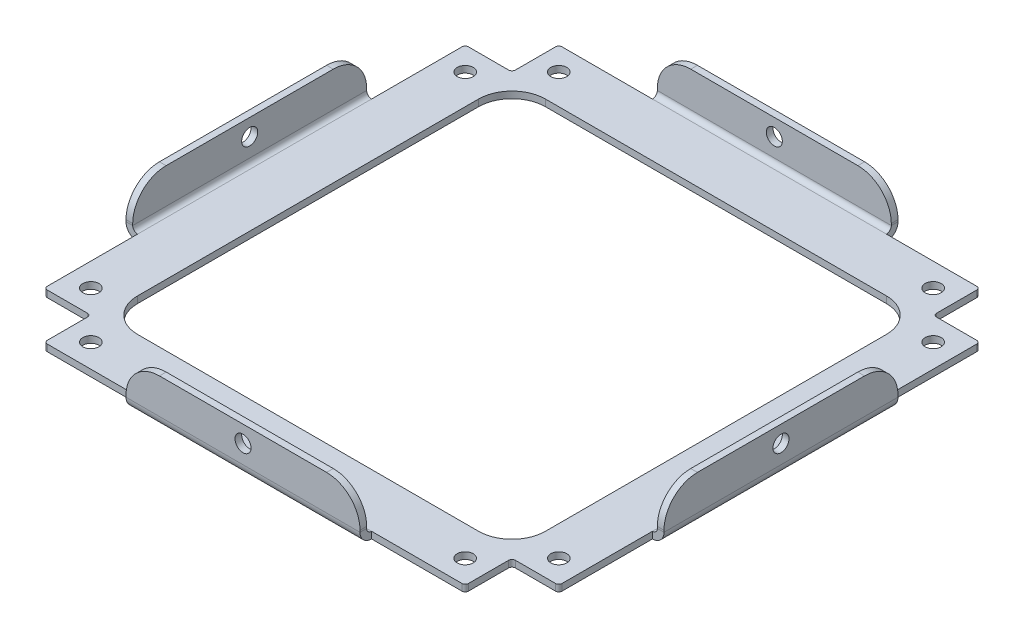
SolidWorks part; units mm, degrees
note: The reader was unsure of these and kept them because the rebuilt part matched: flange length of "Edge-Flange1", "Edge-Flange2", "Edge-Flange3", "Edge-Flange4".
material "6061 Alloy"
ref_plane "Frontal" through (0, 0, 0) normal (0, 0, 1) x (1, 0, 0)
ref_plane "Superior" through (0, 0, 0) normal (0, 1, 0) x (1, 0, 0)
ref_plane "Direito" through (0, 0, 0) normal (1, 0, 0) x (0, 0, -1)
sketch "Sketch1" plane through (0, 0, 0) normal (0, 1, 0) x (1, 0, 0)
  line L1 (-38.5, -38.5) -> (38.5, -38.5)
  line L2 (-38.5, -38.5) -> (-38.5, 38.5)
  line L3 (-38.5, 38.5) -> (38.5, 38.5)
  line L4 (38.5, -38.5) -> (38.5, 38.5)
  line L5 (-38.5, -38.5) -> (38.5, 38.5) construction
  line L6 (-38.5, 38.5) -> (38.5, -38.5) construction
  point P0 (0, 0)
  dimension "D1" = 77
  dimension "D2" = 77
base flange "Base-Flange1" sketch "Sketch1" thickness 1 reverse thickness direction no parameters "D1"=0.7366
edge flange "Edge-Flange1" sketch "Sketch8" flange angle 90 flange length 6 flange position bend outside bend radius 0.7366 thickness 1 relief rectangular parameters "D6"=10
sketch "Sketch8" plane through (0, 0, 38.5) normal (0, 0, 1) x (1, 0, 0)
  line L0 (-38.5, 0) -> (38.5, 0) construction
  line L1 (-17.5, 0) -> (17.5, 0)
  line L2 (-17.5, 0) -> (-17.5, 6)
  line L3 (-17.5, 6) -> (17.5, 6)
  line L4 (17.5, 6) -> (17.5, 0)
  point P6 (0, 0)
  dimension "D1" = 6
  dimension "D2" = 35
bend "EdgeBend1" bend radius 0.7366 bend angle 90 parameters "D5"=1
edge flange "Edge-Flange2" sketch "Sketch11" flange angle 90 flange length 6 flange position bend outside bend radius 0.7366 thickness 1 relief rectangular parameters "D6"=10
sketch "Sketch11" plane through (0, 0, -38.5) normal (0, 0, -1) x (-1, 0, 0)
  line L0 (-38.5, 0) -> (38.5, 0) construction
  line L1 (-17.5, 0) -> (17.5, 0)
  line L2 (-17.5, 0) -> (-17.5, 6)
  line L3 (-17.5, 6) -> (17.5, 6)
  line L4 (17.5, 6) -> (17.5, 0)
  point P6 (0, 0)
  dimension "D1" = 6
  dimension "D2" = 35
bend "EdgeBend2" bend radius 0.7366 bend angle 90 parameters "D5"=2
edge flange "Edge-Flange3" sketch "Sketch14" flange angle 90 flange length 6 flange position bend outside bend radius 0.7366 thickness 1 relief rectangular parameters "D6"=10
sketch "Sketch14" plane through (-38.5, 0, 0) normal (-1, 0, 0) x (0, 0, 1)
  line L0 (-38.5, 0) -> (38.5, 0) construction
  line L1 (-17.5, 0) -> (17.5, 0)
  line L2 (-17.5, 0) -> (-17.5, 6)
  line L3 (-17.5, 6) -> (17.5, 6)
  line L4 (17.5, 6) -> (17.5, 0)
  point P6 (0, 0)
  dimension "D1" = 6
  dimension "D2" = 35
bend "EdgeBend3" bend radius 0.7366 bend angle 90 parameters "D5"=3
edge flange "Edge-Flange4" sketch "Sketch17" flange angle 90 flange length 6 flange position bend outside bend radius 0.7366 thickness 1 relief rectangular parameters "D6"=10
sketch "Sketch17" plane through (38.5, 0, 0) normal (1, 0, 0) x (0, 0, -1)
  line L0 (-38.5, 0) -> (38.5, 0) construction
  line L1 (-17.5, 0) -> (17.5, 0)
  line L2 (-17.5, 0) -> (-17.5, 6)
  line L3 (-17.5, 6) -> (17.5, 6)
  line L4 (17.5, 6) -> (17.5, 0)
  point P6 (0, 0)
  dimension "D1" = 6
  dimension "D2" = 35
bend "EdgeBend4" bend radius 0.7366 bend angle 90 parameters "D5"=4
sketch "Sketch18" plane through (0, 0, 0) normal (0, 1, 0) x (1, 0, 0)
  line L1 (-25.5, -30.5) -> (25.5, -30.5)
  line L2 (-30.5, -25.5) -> (-30.5, 25.5)
  line L3 (-25.5, 30.5) -> (25.5, 30.5)
  line L4 (30.5, -25.5) -> (30.5, 25.5)
  line L5 (-25.5, -25.5) -> (25.5, 25.5) construction
  line L6 (-25.5, 25.5) -> (25.5, -25.5) construction
  line L7 (-38.5, 38.5) -> (-31.5, 38.5)
  line L8 (-38.5, 38.5) -> (-38.5, 31.5)
  line L9 (-38.5, 31.5) -> (-32, 31.5)
  line L10 (-31.5, 38.5) -> (-31.5, 32)
  line L11 (38.5, 38.5) -> (31.5, 38.5)
  line L12 (38.5, 38.5) -> (38.5, 31.5)
  line L13 (38.5, 31.5) -> (32, 31.5)
  line L14 (31.5, 38.5) -> (31.5, 32)
  line L15 (38.5, -38.5) -> (31.5, -38.5)
  line L16 (38.5, -38.5) -> (38.5, -31.5)
  line L17 (38.5, -31.5) -> (32, -31.5)
  line L18 (31.5, -38.5) -> (31.5, -32)
  line L19 (-38.5, -38.5) -> (-31.5, -38.5)
  line L20 (-38.5, -38.5) -> (-38.5, -31.5)
  line L21 (-38.5, -31.5) -> (-32, -31.5)
  line L22 (-31.5, -38.5) -> (-31.5, -32)
  arc A0 (-25.5, 30.5) -> (-30.5, 25.5) centre (-25.5, 25.5) ccw
  arc A1 (25.5, 30.5) -> (30.5, 25.5) centre (25.5, 25.5) cw
  arc A2 (30.5, -25.5) -> (25.5, -30.5) centre (25.5, -25.5) cw
  arc A3 (-25.5, -30.5) -> (-30.5, -25.5) centre (-25.5, -25.5) cw
  arc A4 (-31.5, 32) -> (-32, 31.5) centre (-32, 32) cw
  arc A5 (31.5, 32) -> (32, 31.5) centre (32, 32) ccw
  arc A6 (32, -31.5) -> (31.5, -32) centre (32, -32) ccw
  arc A7 (-32, -31.5) -> (-31.5, -32) centre (-32, -32) cw
  point P0 (0, 0)
  dimension "D1" = 5
  dimension "D2" = 5
  dimension "D3" = 5
  dimension "D4" = 5
  dimension "D7" = 0.5
  dimension "D9" = 0.5
  dimension "D11" = 0.5
  dimension "D13" = 0.5
  dimension "D5" = 61
  dimension "D6" = 61
  dimension "D8" = 7
  dimension "D10" = 7
  dimension "D12" = 7
  dimension "D14" = 7
  dimension "D15" = 7
  dimension "D16" = 7
  dimension "D17" = 7
  dimension "D18" = 7
extrude "Cut-Extrude1" cut sketch "Sketch18" against normal through all normal cut yes
fillet "Fillet1" radius 0.5 8 edges at (31.5, -0.5, -38.5) (38.5, -0.5, -31.5) (38.5, -0.5, 31.5) (31.5, -0.5, 38.5) (-31.5, -0.5, 38.5) (-38.5, -0.5, 31.5) (-38.5, -0.5, -31.5) (-31.5, -0.5, -38.5)
fillet "Fillet2" radius 5 8 edges at (39.7366, 6, 17.5) (39.7366, 6, -17.5) (17.5, 6, -39.7366) (-17.5, 6, -39.7366) (-39.7366, 6, -17.5) (-39.7366, 6, 17.5) (-17.5, 6, 39.7366) (17.5, 6, 39.7366)
hole_wizard "M2 Hole1 - AA" positions "3DSketch1" profile "Sketch25" hole size "M2" standard "DIN" end condition through all
sketch3d "3DSketch1"
  line L0 (-38.5, 0, -31) -> (-38.5, 0, -17.5) construction
  line L1 (-38, 0, -31.5) -> (-32, 0, -31.5) construction
  line L2 (-17.5, 0, -38.5) -> (-31, 0, -38.5) construction
  line L3 (-31.5, 0, -32) -> (-31.5, 0, -38) construction
  line L4 (31.5, 0, -38) -> (31.5, 0, -32) construction
  line L6 (38.5, 0, -17.5) -> (38.5, 0, -31) construction
  line L7 (38, 0, 31.5) -> (32, 0, 31.5) construction
  line L8 (17.5, 0, 38.5) -> (31, 0, 38.5) construction
  point P0 (-35, 0, -28)
  point P2 (-28, 0, -35)
  point P4 (28, 0, -35)
  point P6 (35, 0, -28)
  point P8 (-35, 0, 28)
  point P10 (-28, 0, 35)
  point P12 (28, 0, 35)
  point P14 (35, 0, 28)
  dimension "D1" = 3.5
  dimension "D2" = 3.5
  dimension "D3" = 3.5
  dimension "D4" = 3.5
  dimension "D5" = 3.5
  dimension "D6" = 3.5
  dimension "D7" = 3.5
  dimension "D8" = 3.5
sketch "Sketch25" plane through (-35, 0, -28) normal (1, 0, 0) x (0, 0, 1)
  line L0 (0, 0) -> (0, 1.0001)
  line L1 (0, 1.0001) -> (1.2, 1.0001)
  line L2 (1.2, 1.0001) -> (1.2, 0)
  line L5 (1.2, 0) -> (0, 0)
  line L11 (0, -6.35) -> (0, 107.95) construction
  dimension "Thru Hole Dia." = 2.4
  dimension "Thru Hole Depth" = 1.0001
hole_wizard "M2 Hole2 - AB" positions "Sketch22" profile "Sketch21" hole size "M2" standard "DIN" end condition through all
sketch "Sketch22" plane through (-40.2366, 0, 0) normal (-1, 0, 0) x (0, 0, 1)
  line L0 (12.5, 6) -> (-12.5, 6) construction
  line L1 (17.5, 0.7366) -> (17.5, 1) construction
  point P0 (0, 3.5)
  dimension "D1" = 2.5
  dimension "D2" = 17.5
sketch "Sketch21" plane through (-40.2366, 3.5, 0) normal (0, 1, 0) x (0, 0, 1)
  line L0 (0, 0) -> (0, 80.4732)
  line L1 (0, 80.4732) -> (1.2, 80.4732)
  line L2 (1.2, 80.4732) -> (1.2, 0)
  line L5 (1.2, 0) -> (0, 0)
  line L11 (0, -6.35) -> (0, 107.95) construction
  dimension "Thru Hole Dia." = 2.4
  dimension "Thru Hole Depth" = 80.4732
hole_wizard "M2 Hole3 - AC" positions "Sketch24" profile "Sketch23" hole size "M2" standard "DIN" end condition through all
sketch "Sketch24" plane through (0, 0, 40.2366) normal (0, 0, 1) x (1, 0, 0)
  line L0 (12.5, 6) -> (-12.5, 6) construction
  line L1 (17.5, 0.7366) -> (17.5, 1) construction
  point P0 (0, 3.5)
  dimension "D1" = 2.5
  dimension "D2" = 17.5
sketch "Sketch23" plane through (0, 3.5, 40.2366) normal (1, 0, 0) x (0, -1, 0)
  line L0 (0, 0) -> (0, 80.4732)
  line L1 (0, 80.4732) -> (1.2, 80.4732)
  line L2 (1.2, 80.4732) -> (1.2, 0)
  line L5 (1.2, 0) -> (0, 0)
  line L11 (0, -6.35) -> (0, 107.95) construction
  dimension "Thru Hole Dia." = 2.4
  dimension "Thru Hole Depth" = 80.4732
sketch "Bend-Lines1" [suppressed] plane through (0, 0, 0) normal (0, 1, 0) x (1, 0, 0)
sketch "Bounding-Box1" [suppressed] plane through (0, 0, 0) normal (0, 1, 0) x (1, 0, 0)
sheet metal parameters "Sheet-Metal(1)" thickness 1 parameters "D1"=0.7366
flat pattern "Flat-Pattern(1)" [suppressed]
sketch "Bend-Lines2" plane through (0, 0, 0) normal (0, 1, 0) x (1, 0, 0)
sketch "Bounding-Box2" [suppressed] plane through (0, 0, 0) normal (0, 1, 0) x (1, 0, 0)
sheet metal parameters "Sheet-Metal(2)" thickness 1 parameters "D1"=0.7366
flat pattern "Flat-Pattern(1)" [suppressed]
sketch "Bend-Lines2" plane through (0, 0, 0) normal (0, 1, 0) x (1, 0, 0)
sketch "Bounding-Box2" [suppressed] plane through (0, 0, 0) normal (0, 1, 0) x (1, 0, 0)
bend of the flat pattern "Flatten-<EdgeBend1>1"
sheet metal parameters "Sheet-Metal(3)" thickness 1 parameters "D1"=0.7366
flat pattern "Flat-Pattern(1)"
sketch "Bend-Lines2" plane through (0, 0, 0) normal (0, 1, 0) x (1, 0, 0)
  line L0 (17.5, 39.4712) -> (-17.5, 39.4712) construction
  line L1 (-17.5, -39.4712) -> (17.5, -39.4712) construction
  line L2 (17.5, 39.4712) -> (-17.5, 39.4712) construction
  line L3 (-17.5, -39.4712) -> (17.5, -39.4712) construction
sketch3d "Bounding-Box2" [suppressed]
  line L0 (-38.5, -46.7058, 0) -> (-38.5, 46.7058, 0) construction
  line L1 (38.5, -46.7058, 0) -> (38.5, 46.7058, 0) construction
  line L2 (-38.5, -46.7058, 0) -> (38.5, -46.7058, 0) construction
  line L3 (-38.5, 46.7058, 0) -> (38.5, 46.7058, 0) construction
bend of the flat pattern "Flatten-<EdgeBend1>1"
bend of the flat pattern "Flatten-<EdgeBend2>1"
sheet metal parameters "Sheet-Metal(4)" thickness 1 parameters "D1"=0.7366
flat pattern "Flat-Pattern(1)" [suppressed]
sketch "Bend-Lines2" plane through (0, 0, 0) normal (0, 1, 0) x (1, 0, 0)
  line L0 (17.5, 39.4712) -> (-17.5, 39.4712) construction
  line L1 (-17.5, -39.4712) -> (17.5, -39.4712) construction
  line L2 (17.5, 39.4712) -> (-17.5, 39.4712) construction
  line L3 (-17.5, -39.4712) -> (17.5, -39.4712) construction
sketch3d "Bounding-Box2" [suppressed]
  line L0 (-38.5, -46.7058, 0) -> (-38.5, 46.7058, 0) construction
  line L1 (38.5, -46.7058, 0) -> (38.5, 46.7058, 0) construction
  line L2 (-38.5, -46.7058, 0) -> (38.5, -46.7058, 0) construction
  line L3 (-38.5, 46.7058, 0) -> (38.5, 46.7058, 0) construction
bend of the flat pattern "Flatten-<EdgeBend1>1"
bend of the flat pattern "Flatten-<EdgeBend2>1"
bend of the flat pattern "Flatten-<EdgeBend3>1"
sheet metal parameters "Sheet-Metal(5)" thickness 1 parameters "D1"=0.7366
flat pattern "Flat-Pattern(1)" [suppressed]
sketch "Bend-Lines2" plane through (0, 0, 0) normal (0, 1, 0) x (1, 0, 0)
  line L0 (17.5, 39.4712) -> (-17.5, 39.4712) construction
  line L1 (-17.5, -39.4712) -> (17.5, -39.4712) construction
  line L2 (17.5, 39.4712) -> (-17.5, 39.4712) construction
  line L3 (-17.5, -39.4712) -> (17.5, -39.4712) construction
sketch3d "Bounding-Box2" [suppressed]
  line L0 (-38.5, -46.7058, 0) -> (-38.5, 46.7058, 0) construction
  line L1 (38.5, -46.7058, 0) -> (38.5, 46.7058, 0) construction
  line L2 (-38.5, -46.7058, 0) -> (38.5, -46.7058, 0) construction
  line L3 (-38.5, 46.7058, 0) -> (38.5, 46.7058, 0) construction
bend of the flat pattern "Flatten-<EdgeBend1>1"
bend of the flat pattern "Flatten-<EdgeBend2>1"
bend of the flat pattern "Flatten-<EdgeBend3>1"
bend of the flat pattern "Flatten-<EdgeBend4>1"
sheet metal parameters "Sheet-Metal(6)" thickness 1 parameters "D1"=0.7366
flat pattern "Flat-Pattern(1)"
sketch "Bend-Lines2" plane through (0, 0, 0) normal (0, 1, 0) x (1, 0, 0)
  line L0 (17.5, 39.4712) -> (-17.5, 39.4712) construction
  line L1 (-17.5, -39.4712) -> (17.5, -39.4712) construction
  line L2 (17.5, 39.4712) -> (-17.5, 39.4712) construction
  line L3 (-17.5, -39.4712) -> (17.5, -39.4712) construction
  line L4 (39.4712, -17.5) -> (39.4712, 17.5) construction
  line L5 (-39.4712, 17.5) -> (-39.4712, -17.5) construction
  line L6 (39.4712, -17.5) -> (39.4712, 17.5) construction
  line L7 (-39.4712, 17.5) -> (-39.4712, -17.5) construction
sketch3d "Bounding-Box2" [suppressed]
  line L0 (-46.7059, 46.7058, 0) -> (46.7058, 46.7059, 0) construction
  line L1 (-46.7058, -46.7059, 0) -> (46.7059, -46.7058, 0) construction
  line L2 (-46.7059, 46.7058, 0) -> (-46.7058, -46.7059, 0) construction
  line L3 (46.7058, 46.7059, 0) -> (46.7059, -46.7058, 0) construction
bend of the flat pattern "Flatten-<EdgeBend1>1"
bend of the flat pattern "Flatten-<EdgeBend2>1"
bend of the flat pattern "Flatten-<EdgeBend3>1"
bend of the flat pattern "Flatten-<EdgeBend4>1"
sheet metal parameters "Sheet-Metal(8)" thickness 1 parameters "D1"=0.7366
flat pattern "Flat-Pattern(1)"
sketch "Bend-Lines2" plane through (0, 0, 0) normal (0, 1, 0) x (1, 0, 0)
  line L0 (17.5, 39.4712) -> (-17.5, 39.4712) construction
  line L1 (-17.5, -39.4712) -> (17.5, -39.4712) construction
  line L2 (17.5, 39.4712) -> (-17.5, 39.4712) construction
  line L3 (-17.5, -39.4712) -> (17.5, -39.4712) construction
  line L4 (39.4712, -17.5) -> (39.4712, 17.5) construction
  line L5 (-39.4712, 17.5) -> (-39.4712, -17.5) construction
  line L6 (39.4712, -17.5) -> (39.4712, 17.5) construction
  line L7 (-39.4712, 17.5) -> (-39.4712, -17.5) construction
sketch3d "Bounding-Box2" [suppressed]
  line L0 (-46.7059, 46.7058, 0) -> (46.7058, 46.7059, 0) construction
  line L1 (-46.7058, -46.7059, 0) -> (46.7059, -46.7058, 0) construction
  line L2 (-46.7059, 46.7058, 0) -> (-46.7058, -46.7059, 0) construction
  line L3 (46.7058, 46.7059, 0) -> (46.7059, -46.7058, 0) construction
bend of the flat pattern "Flatten-<EdgeBend1>1"
bend of the flat pattern "Flatten-<EdgeBend2>1"
bend of the flat pattern "Flatten-<EdgeBend3>1"
bend of the flat pattern "Flatten-<EdgeBend4>1"
sheet metal parameters "Sheet-Metal(9)" thickness 1 parameters "D1"=0.7366
flat pattern "Flat-Pattern(1)"
sketch "Bend-Lines2" plane through (0, 0, 0) normal (0, 1, 0) x (1, 0, 0)
  line L0 (17.5, 39.4712) -> (-17.5, 39.4712) construction
  line L1 (-17.5, -39.4712) -> (17.5, -39.4712) construction
  line L2 (17.5, 39.4712) -> (-17.5, 39.4712) construction
  line L3 (-17.5, -39.4712) -> (17.5, -39.4712) construction
  line L4 (39.4712, -17.5) -> (39.4712, 17.5) construction
  line L5 (-39.4712, 17.5) -> (-39.4712, -17.5) construction
  line L6 (39.4712, -17.5) -> (39.4712, 17.5) construction
  line L7 (-39.4712, 17.5) -> (-39.4712, -17.5) construction
sketch3d "Bounding-Box2" [suppressed]
  line L0 (-45.7059, 45.7058, 0) -> (45.7058, 45.7059, 0) construction
  line L1 (-45.7058, -45.7059, 0) -> (45.7059, -45.7058, 0) construction
  line L2 (-45.7059, 45.7058, 0) -> (-45.7058, -45.7059, 0) construction
  line L3 (45.7058, 45.7059, 0) -> (45.7059, -45.7058, 0) construction
bend of the flat pattern "Flatten-<EdgeBend1>1"
bend of the flat pattern "Flatten-<EdgeBend2>1"
bend of the flat pattern "Flatten-<EdgeBend3>1"
bend of the flat pattern "Flatten-<EdgeBend4>1"
sheet metal parameters "Sheet-Metal(10)" thickness 1 parameters "D1"=0.7366
flat pattern "Flat-Pattern(1)"
sketch "Bend-Lines2" plane through (0, 0, 0) normal (0, 1, 0) x (1, 0, 0)
  line L0 (17.5, 39.4712) -> (-17.5, 39.4712) construction
  line L1 (-17.5, -39.4712) -> (17.5, -39.4712) construction
  line L2 (17.5, 39.4712) -> (-17.5, 39.4712) construction
  line L3 (-17.5, -39.4712) -> (17.5, -39.4712) construction
  line L4 (39.4712, -17.5) -> (39.4712, 17.5) construction
  line L5 (-39.4712, 17.5) -> (-39.4712, -17.5) construction
  line L6 (39.4712, -17.5) -> (39.4712, 17.5) construction
  line L7 (-39.4712, 17.5) -> (-39.4712, -17.5) construction
sketch3d "Bounding-Box2" [suppressed]
  line L0 (-46.7059, 46.7058, 0) -> (46.7058, 46.7059, 0) construction
  line L1 (-46.7058, -46.7059, 0) -> (46.7059, -46.7058, 0) construction
  line L2 (-46.7059, 46.7058, 0) -> (-46.7058, -46.7059, 0) construction
  line L3 (46.7058, 46.7059, 0) -> (46.7059, -46.7058, 0) construction
bend of the flat pattern "Flatten-<EdgeBend1>1"
bend of the flat pattern "Flatten-<EdgeBend2>1"
bend of the flat pattern "Flatten-<EdgeBend3>1"
bend of the flat pattern "Flatten-<EdgeBend4>1"
